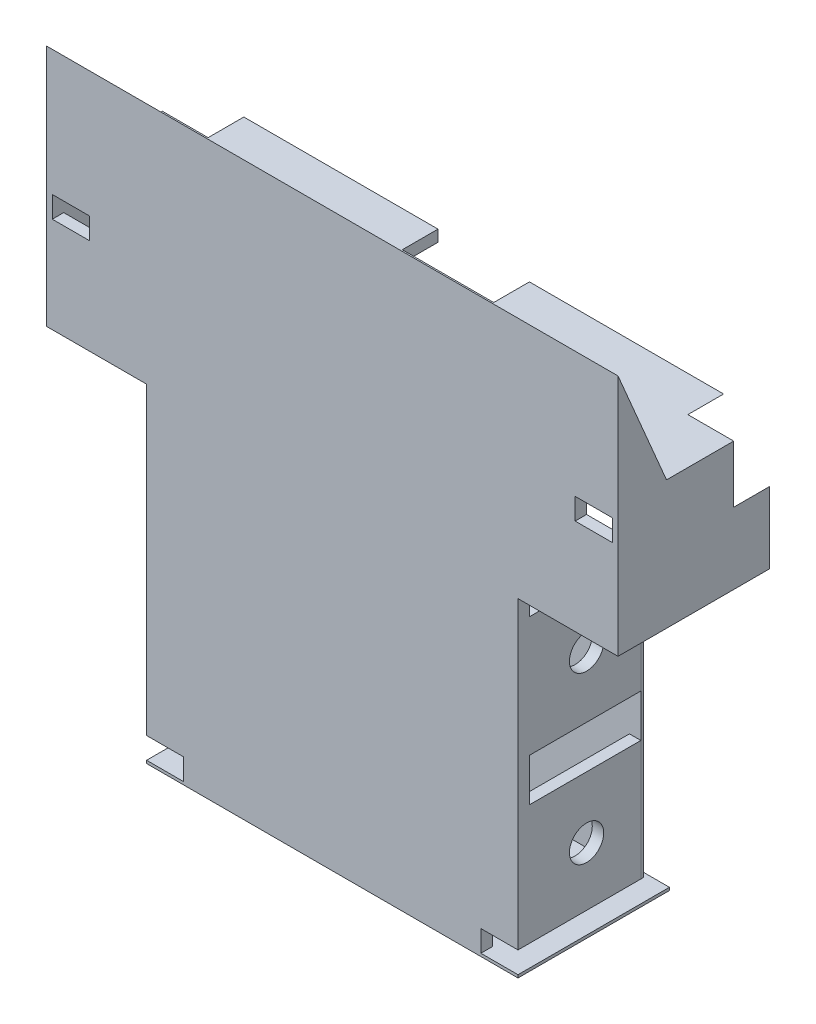
SolidWorks part; units mm, degrees
material "Malleable Cast Iron"
ref_plane "Alzado" through (0, 0, 0) normal (0, 0, 1) x (1, 0, 0)
ref_plane "Planta" through (0, 0, 0) normal (0, 1, 0) x (1, 0, 0)
ref_plane "Vista lateral" through (0, 0, 0) normal (1, 0, 0) x (0, 0, -1)
sketch "Sketch1" plane through (0, 0, 0) normal (0, 0, 1) x (1, 0, 0)
  line L0 (0, 160) -> (200, 160)
  line L5 (0, 0) -> (200, 0)
  line L6 (0, 0) -> (0, 200)
  line L7 (0, 200) -> (200, 200)
  line L8 (200, 0) -> (200, 200)
  line L9 (0, 0) -> (35, 0)
  line L10 (0, 0) -> (0, 55)
  line L11 (0, 55) -> (35, 55)
  line L12 (35, 0) -> (35, 55)
  line L13 (200, 0) -> (165, 0)
  line L14 (200, 0) -> (200, 55)
  line L15 (200, 55) -> (165, 55)
  line L16 (165, 0) -> (165, 55)
  line L17 (0, 135.9584) -> (24.0416, 160)
  line L19 (175.9584, 160) -> (200, 135.9584)
  line L20 (35, 55) -> (35, 60)
  line L21 (0, 115) -> (35, 115)
  line L22 (0, 115) -> (0, 60)
  line L23 (0, 60) -> (35, 60)
  line L24 (35, 115) -> (35, 60)
  line L25 (200, 115) -> (165, 115)
  line L26 (200, 115) -> (200, 60)
  line L27 (200, 60) -> (165, 60)
  line L28 (165, 115) -> (165, 60)
  line L29 (165, 60) -> (165, 55)
  dimension "D1" = 200
  dimension "D2" = 200
  dimension "D3" = 55
  dimension "D4" = 55
  dimension "D5" = 35
  dimension "D6" = 35
  dimension "D7" = 40
  dimension "D8" = 45
  dimension "D9" = 34
  dimension "D10" = 45
  dimension "D11" = 55
  dimension "D12" = 35
  dimension "D13" = 5
  dimension "D14" = 5
extrude "Boss-Extrude1" add sketch "Sketch1" along normal blind 4 contours L28 L25 L8 L0 L6 L21 L24 L23 L11 L12 L5 L16 L15 L27 region at (100, 85.9694, 0)
sketch "Sketch3" plane through (0, 0, 4) normal (0, 0, 1) x (1, 0, 0)
  line L1 (0, 0) -> (200, 0)
  line L2 (0, 0) -> (0, 1)
  line L3 (0, 160) -> (200, 160)
  line L4 (200, 0) -> (200, 1)
  line L5 (200, 115) -> (198, 115)
  line L6 (2, 156) -> (198, 156)
  line L7 (2, 156) -> (2, 115)
  line L8 (1, 1) -> (199, 1)
  line L9 (198, 156) -> (198, 115)
  line L10 (199, 1) -> (200, 1)
  line L11 (1, 1) -> (0, 1)
  line L12 (0, 115) -> (2, 115)
  line L13 (0, 115) -> (0, 160)
  line L14 (200, 115) -> (200, 160)
  line L15 (200, 115) -> (200, 135.9584) construction
  line L16 (24.0416, 160) -> (175.9584, 160) construction
  dimension "D2" = 1
  dimension "D3" = 2
  dimension "D4" = 2
  dimension "D5" = 4
extrude "Boss-Extrude2" add sketch "Sketch3" against normal blind 53
sketch "Sketch4" plane through (200, 0, 0) normal (1, 0, 0) x (0, 0, -1)
  line L0 (-4, 160) -> (-4, 200)
  line L1 (-4, 200) -> (12.979, 160)
  line L3 (12.979, 160) -> (-4, 160)
  line L4 (49, 160) -> (-4, 160) construction
  line L5 (-4, 115) -> (-4, 160) construction
  point P6 (-0.0305, 200)
  dimension "D1" = 23
  dimension "D2" = 40
extrude "Boss-Extrude4" add sketch "Sketch4" against normal up to surface (200 mm away) up to face at (0, 0.5, -22.5)
ref_axis "Axis1" through (179.9584, 156, 0) along (0.7071, -0.7071, 0)
ref_axis "Axis2" through (0, 135.9584, 0) along (0.7071, 0.7071, 0)
ref_plane "Plane1" through (-67.9792, 67.9792, 0) normal (-0.7071, 0.7071, 0) x (0.7071, 0.7071, 0)
sketch "Sketch5" plane through (-67.9792, 67.9792, 0) normal (-0.7071, 0.7071, 0) x (0.7071, 0.7071, 0)
  line L1 (98.9655, 36.5) -> (124.4802, 36.5)
  line L2 (98.9655, 36.5) -> (98.9655, 49)
  line L3 (98.9655, 49) -> (124.4802, 49)
  line L4 (124.4802, 36.5) -> (124.4802, 49)
  line L8 (111.7229, 49) -> (82.7315, 49) construction
  dimension "D2" = 12.5
extrude "Cut-Extrude1" cut sketch "Sketch5" along normal blind 20
ref_plane "Plane2" through (167.9792, 167.9792, 0) normal (0.7071, 0.7071, 0) x (0, 0, -1)
sketch "Sketch6" plane through (167.9792, 167.9792, 0) normal (0.7071, 0.7071, 0) x (0, 0, -1)
  line L1 (36.5, -16.9411) -> (49, -16.9411)
  line L2 (36.5, -16.9411) -> (36.5, -42.4558)
  line L3 (36.5, -42.4558) -> (49, -42.4558)
  line L4 (49, -16.9411) -> (49, -42.4558)
  line L5 (49, -141.4214) -> (49, -140.7142) construction
  dimension "D2" = 12.5
extrude "Cut-Extrude2" cut sketch "Sketch6" along normal blind 20
sketch "Sketch7" plane through (0, 155, 0) normal (0, 1, 0) x (1, 0, 0)
  line L1 (84, 36.5) -> (116, 36.5)
  line L2 (84, 36.5) -> (84, 49)
  line L3 (84, 49) -> (116, 49)
  line L4 (116, 36.5) -> (116, 49)
  line L5 (84, 36.5) -> (116, 49) construction
  line L6 (84, 49) -> (116, 36.5) construction
  line L7 (200, 36.5) -> (200, 12.979) construction
  line L8 (183.9584, 49) -> (16.0416, 49) construction
  point P0 (100, 42.75)
  dimension "D1" = 12.5
  dimension "D2" = 32
  dimension "D3" = 100
extrude "Cut-Extrude3" cut sketch "Sketch7" along normal blind 8 and the other way blind 6.482
sketch "Sketch8" plane through (0, 0, 4) normal (0, 0, 1) x (1, 0, 0)
  line L0 (20.0416, 156) -> (2, 156)
  line L1 (2, 156) -> (2, 137.9584)
  line L2 (2, 137.9584) -> (20.0416, 156)
  line L3 (179.9584, 156) -> (198, 156)
  line L4 (198, 156) -> (198, 137.9584)
  line L5 (198, 137.9584) -> (179.9584, 156)
extrude "Boss-Extrude5" add sketch "Sketch8" against normal blind 4
sketch "Sketch9" plane through (0, 0, 0) normal (0, 0, -1) x (-1, 0, 0)
  line L0 (-35, 1) -> (-165, 1) construction
  line L1 (-35.5503, 107.5) -> (-39.5503, 107.5)
  line L2 (-35.5503, 107.5) -> (-35.5503, 8.5)
  line L3 (-35.5503, 8.5) -> (-39.5503, 8.5)
  line L4 (-39.5503, 107.5) -> (-39.5503, 8.5)
  line L6 (-165, 107.5) -> (-161, 107.5)
  line L7 (-165, 107.5) -> (-165, 8.5)
  line L8 (-165, 8.5) -> (-161, 8.5)
  line L9 (-161, 107.5) -> (-161, 8.5)
  line L10 (-198, 115) -> (-165, 115) construction
  line L11 (-2, 115) -> (-35, 115) construction
  point P14 (-163, 8.5)
  dimension "D1" = 4
  dimension "D2" = 4
  dimension "D3" = 7.5
  dimension "D4" = 7.5
  dimension "D5" = 7.5
  dimension "D6" = 7.5
extrude "Boss-Extrude6" add sketch "Sketch9" along normal blind 39
sketch "Sketch10" plane through (165, 0, 0) normal (1, 0, 0) x (0, 0, -1)
  line L0 (39, 107.5) -> (39, 8.5) construction
  line L1 (39, 65.5) -> (0, 65.5)
  line L2 (39, 65.5) -> (39, 50.5)
  line L3 (39, 50.5) -> (0, 50.5)
  line L4 (0, 65.5) -> (0, 50.5)
  line L8 (0, 8.5) -> (0, 107.5) construction
  line L9 (39, 8.5) -> (0, 8.5) construction
  dimension "D1" = 15
  dimension "D2" = 42
extrude "Cut-Extrude5" cut sketch "Sketch10" against normal blind 137
sketch "Sketch12" plane through (0, 1, 0) normal (0, 1, 0) x (1, 0, 0)
  line L1 (35, -4) -> (0, -4)
  line L2 (35, -4) -> (35, 49)
  line L3 (35, 49) -> (0, 49)
  line L4 (0, -4) -> (0, 49)
  line L5 (165, -4) -> (200, -4)
  line L6 (165, -4) -> (165, 49)
  line L7 (165, 49) -> (200, 49)
  line L8 (200, -4) -> (200, 49)
extrude "Cut-Extrude6" cut sketch "Sketch12" against normal blind 8
sketch "Sketch13" plane through (165, 0, 0) normal (1, 0, 0) x (0, 0, -1)
  line L0 (-4, 115) -> (-4, 0) construction
  line L1 (39, 107.5) -> (0, 107.5) construction
  line L2 (39, 8.5) -> (0, 8.5) construction
  circle A0 centre (20, 87) radius 6
  circle A1 centre (20, 29) radius 6
  dimension "D1" = 12
  dimension "D2" = 24
  dimension "D3" = 20.5
  dimension "D4" = 24
  dimension "D5" = 20.5
extrude "Cut-Extrude7" cut sketch "Sketch13" against normal blind 135
sketch "Sketch14" plane through (0, 0, -49) normal (0, 0, -1) x (-1, 0, 0)
  line L1 (0, 0) -> (-200, 0)
  line L2 (0, 0) -> (0, 160)
  line L3 (0, 160) -> (-200, 160)
  line L4 (-200, 0) -> (-200, 160)
  point P5 (0, 0)
sketch "Sketch15" plane through (0, 0, -39) normal (0, 0, -1) x (-1, 0, 0)
  line L1 (-165, 107.5) -> (-35.5503, 107.5)
  line L2 (-165, 107.5) -> (-165, 8.5)
  line L3 (-165, 8.5) -> (-35.5503, 8.5)
  line L4 (-35.5503, 107.5) -> (-35.5503, 8.5)
extrude "Boss-Extrude7" add sketch "Sketch15" along normal blind 1
sketch "Sketch16" plane through (165, 0, 0) normal (1, 0, 0) x (0, 0, -1)
  line L0 (39, 107.5) -> (39, 8.5)
  line L1 (40, 107.5) -> (0, 107.5) construction
  line L2 (40, 8.5) -> (0, 8.5) construction
  line L3 (39, 65.5) -> (39, 50.5) construction
split "Split1" trim tools "Sketch16" bodies to split 140 resulting bodies 141 142
sketch "Sketch17" plane through (0, 0, 0) normal (0, 0, -1) x (-1, 0, 0)
  line L0 (-179.9584, 156) -> (-198, 156) construction
  line L1 (-198, 156) -> (-185, 156)
  line L2 (-198, 156) -> (-198, 148.5)
  line L3 (-198, 148.5) -> (-185, 148.5)
  line L4 (-185, 156) -> (-185, 148.5)
  line L5 (-198, 156) -> (-198, 137.9584) construction
  line L7 (-2, 156) -> (-15, 156)
  line L8 (-2, 156) -> (-2, 148.5)
  line L9 (-2, 148.5) -> (-15, 148.5)
  line L10 (-15, 156) -> (-15, 148.5)
  line L11 (-165, 1) -> (-152, 1)
  line L12 (-165, 1) -> (-165, 8.5)
  line L13 (-165, 8.5) -> (-152, 8.5)
  line L14 (-152, 1) -> (-152, 8.5)
  line L15 (-35, 1) -> (-48, 1)
  line L16 (-35, 1) -> (-35, 8.5)
  line L17 (-35, 8.5) -> (-48, 8.5)
  line L18 (-48, 1) -> (-48, 8.5)
  dimension "D1" = 13
  dimension "D2" = 7.5
extrude "Cut-Extrude8" cut sketch "Sketch17" against normal blind 10
